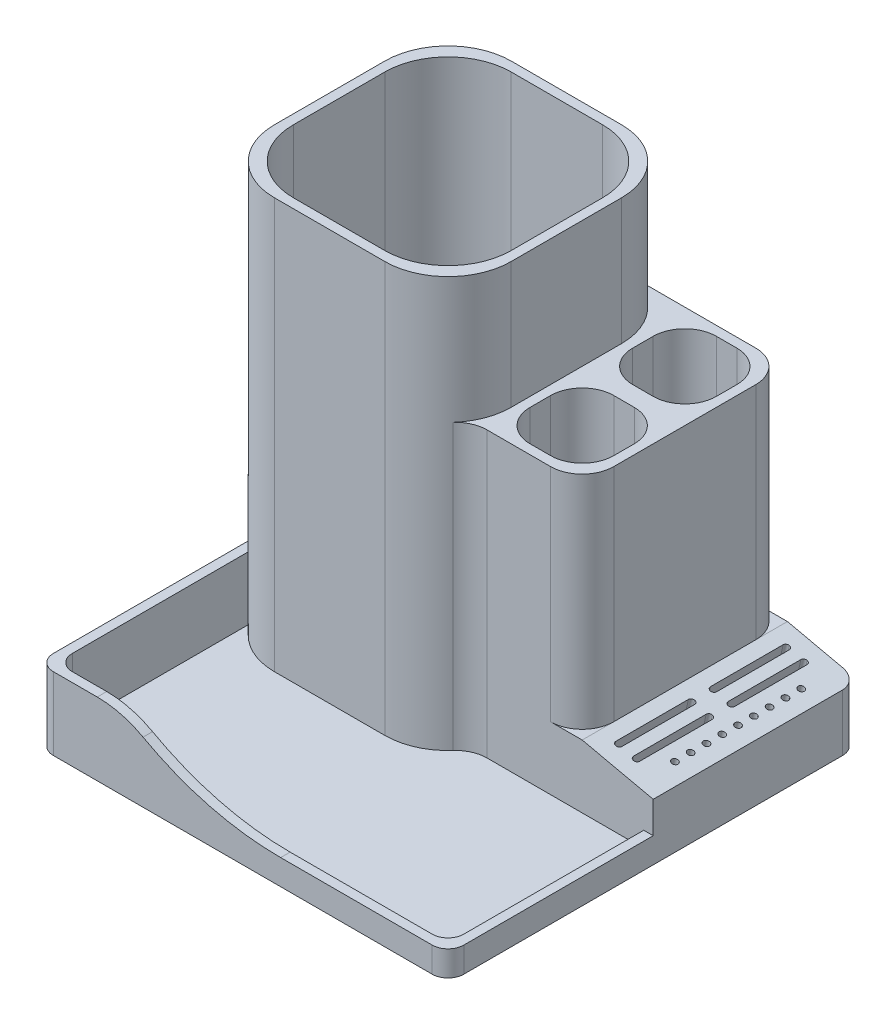
SolidWorks part; units mm, degrees
ref_plane "Спереди" through (0, 0, 0) normal (0, 0, 1) x (1, 0, 0)
ref_plane "Сверху" through (0, 0, 0) normal (0, 1, 0) x (1, 0, 0)
ref_plane "Справа" through (0, 0, 0) normal (1, 0, 0) x (0, 0, -1)
sketch "Эскиз1" plane through (0, 0, 0) normal (0, 1, 0) x (1, 0, 0)
  line L1 (0, 0) -> (-130, 0)
  line L2 (0, 0) -> (0, 130)
  line L3 (0, 130) -> (-130, 130)
  line L4 (-130, 0) -> (-130, 130)
  dimension "D1" = 130
  dimension "D2" = 130
extrude "Бобышка-Вытянуть1" add sketch "Эскиз1" along normal blind 3
sketch "Эскиз2" plane through (0, 3, 0) normal (0, 1, 0) x (1, 0, 0)
  line L0 (-130, 55) -> (-55, 130) construction
  line L1 (-130, 130) -> (-55, 130)
  line L2 (-130, 130) -> (-130, 55)
  line L3 (-130, 55) -> (-55, 55)
  line L4 (-55, 130) -> (-55, 55)
  line L5 (-130, 130) -> (-55, 55) construction
  line L6 (-55, 55) -> (-54.4683, 54.7826) construction
  line L8 (-127, 127) -> (-58, 127)
  line L9 (-127, 127) -> (-127, 58)
  line L10 (-127, 58) -> (-58, 58)
  line L11 (-58, 127) -> (-58, 58)
  line L12 (-127, 127) -> (-58, 58) construction
  line L13 (-127, 58) -> (-58, 127) construction
  point P5 (-92.5, 92.5)
  dimension "D1" = 3
  dimension "D2" = 75
extrude "Бобышка-Вытянуть2" add sketch "Эскиз2" along normal blind 130
sketch "Эскиз3" plane through (0, 3, 0) normal (0, 1, 0) x (1, 0, 0)
  line L0 (-55, 97.5) -> (-22.5, 130) construction
  line L1 (-55, 130) -> (-22.5, 130)
  line L2 (-55, 130) -> (-55, 97.5)
  line L3 (-55, 97.5) -> (-22.5, 97.5)
  line L4 (-22.5, 130) -> (-22.5, 97.5)
  line L5 (-55, 97.5) -> (-22.5, 97.5)
  line L6 (-55, 97.5) -> (-55, 65)
  line L7 (-55, 65) -> (-22.5, 65)
  line L8 (-22.5, 97.5) -> (-22.5, 65)
  line L9 (-22.5, 130) -> (-31.9264, 129.8019) construction
  line L10 (-55, 130) -> (-22.5, 97.5) construction
  line L11 (-55, 65) -> (-22.5, 97.5) construction
  line L12 (-55, 97.5) -> (-22.5, 65) construction
  line L14 (-52, 127) -> (-25.5, 127)
  line L15 (-52, 127) -> (-52, 100.5)
  line L16 (-52, 100.5) -> (-25.5, 100.5)
  line L17 (-25.5, 127) -> (-25.5, 100.5)
  line L18 (-52, 127) -> (-25.5, 100.5) construction
  line L19 (-52, 100.5) -> (-25.5, 127) construction
  line L20 (-52, 94.5) -> (-25.5, 94.5)
  line L21 (-52, 94.5) -> (-52, 68)
  line L22 (-52, 68) -> (-25.5, 68)
  line L23 (-25.5, 94.5) -> (-25.5, 68)
  line L24 (-52, 94.5) -> (-25.5, 68) construction
  line L25 (-52, 68) -> (-25.5, 94.5) construction
  point P7 (-38.75, 113.75)
  point P13 (-38.75, 81.25)
  line M1 (-55, 130) -> (-55, 55)
  line M6 (0, 130) -> (-55, 130)
  dimension "D1" = 32.5
  dimension "D2" = 32.5
  dimension "D3" = 32.5
  dimension "D4" = 3
  dimension "D5" = 3
  dimension "D6" = 3
  dimension "D7" = 3
extrude "Бобышка-Вытянуть3" add sketch "Эскиз3" along normal blind 90 contours L4 L3 L14 L17 L16 L15 M6 M1 | L8 L3 L7 L20 L23 L22 L21 M1 region at (-38.75, 3, -129.5404) region at (-38.75, 3, -97.0404)
fillet "Скругление2" radius 20 2 edges at (-130, 66.5, -130) (-127, 68, -127)
fillet "Скругление3" radius 20 4 edges at (-58, 68, -58) (-55, 68, -55) (-58, 68, -127)
sketch "Эскиз4" plane through (0, 3, 0) normal (0, 1, 0) x (1, 0, 0)
  line L0 (-130, 0) -> (0, 0) construction
  line L1 (-130, 55) -> (-127, 55)
  line L2 (-130, 55) -> (-130, 0)
  line L3 (-130, 0) -> (-127, 0)
  line L4 (-127, 55) -> (-127, 0)
  line L5 (0, 0) -> (0, 130) construction
  line L6 (-127, 0) -> (0, 0)
  line L7 (-127, 0) -> (-127, 3)
  line L8 (-127, 3) -> (0, 3)
  line L9 (0, 0) -> (0, 3)
  line L15 (0, 3) -> (-3, 3)
  line L16 (0, 3) -> (0, 65)
  line L17 (0, 65) -> (-3, 65)
  line L18 (-3, 3) -> (-3, 65)
  line L19 (-22.5, 65) -> (0, 65)
  line M2 (-75, 55) -> (-130, 55)
  line M3 (-130, 55) -> (-130, 0)
  line M4 (-130, 0) -> (0, 0)
  line M5 (0, 0) -> (0, 130)
  dimension "D1" = 3
  dimension "D2" = 3
  dimension "D3" = 3
fillet "Скругление6" radius 10 9 edges at (-57.6795, 48, -65) (-25.5, 48, -100.5) (-25.5, 48, -94.5) (-52, 48, -94.5) (-52, 48, -100.5) (-52, 48, -127) (-52, 48, -68) (-25.5, 48, -68) (-25.5, 48, -127)
extrude "Бобышка-Вытянуть7" add sketch "Эскиз4" along normal blind 20 contours L18 L8 L17 M5 | L8 L4 M4 M5 | L4 M2 M3 M4 region at (-128.5, 3, -27.5) region at (-63.5, 3, -1.5) region at (-1.5, 3, -34)
sketch "Эскиз14" plane through (0, 3, 0) normal (0, 1, 0) x (1, 0, 0)
  line L1 (-22.5, 130) -> (0, 130)
  line L2 (-22.5, 130) -> (-22.5, 65)
  line L3 (-22.5, 65) -> (0, 65)
  line L4 (0, 130) -> (0, 65)
extrude "Бобышка-Вытянуть8" add sketch "Эскиз14" along normal blind 20
sketch "Эскиз15" plane through (0, 0, 0) normal (0, 0, 1) x (1, 0, 0)
  line L0 (-130, 23) -> (0, 23) construction
  line L1 (-102.7518, 23) -> (0, 23)
  line L2 (-102.7518, 23) -> (-102.7518, 8)
  line L3 (-102.7518, 8) -> (0, 8)
  line L4 (0, 23) -> (0, 8)
  line L5 (0, 23) -> (0, 0) construction
  point P9 (0, 0)
  line M2 (0, 0) -> (0, 23)
  line M3 (0, 23) -> (-130, 23)
  dimension "D1" = 8
extrude "Вырез-Вытянуть6" cut sketch "Эскиз15" against normal blind 3 contours L3 M3 M2 region at (-51.3759, 15.5, 0)
fillet "Скругление7" radius 90 1 edges at (-102.7518, 8, -1.5)
fillet "Скругление8" radius 30 1 edges at (-102.7518, 23, -1.5)
sketch "Эскиз17" plane through (0, 0, 0) normal (1, 0, 0) x (0, 0, -1)
  line L1 (3, 8) -> (65, 8)
  line L2 (3, 8) -> (3, 23)
  line L3 (3, 23) -> (65, 23)
  line L4 (65, 8) -> (65, 23)
  point P6 (0, 0)
  point P7 (0, 0)
extrude "Вырез-Вытянуть8" cut sketch "Эскиз17" against normal blind 3
fillet "Скругление9" radius 5 5 edges at (0, 11.5, -130) (-3, 5.5, -3) (0, 4, 0) (-127, 13, -3) (-130, 11.5, 0)
fillet "Скругление11" radius 20 1 edges at (-127, 68, -58)
fillet "Скругление12" radius 20 1 edges
fillet "Скругление13" radius 10 2 edges at (-22.5, 58, -65) (-22.5, 58, -130)
sketch "Эскиз18" plane through (0, 0, -65) normal (0, 0, 1) x (1, 0, 0)
  line L0 (-22.5, 23) -> (0, 18)
  line L1 (0, 23) -> (-32.5, 23) construction
  line L2 (-22.5, 93) -> (-22.5, 23) construction
  line L3 (0, 8) -> (0, 23) construction
  line L4 (0, 18) -> (0, 23)
  line L5 (0, 23) -> (-22.5, 23)
  dimension "D1" = 5
extrude "Вырез-Вытянуть9" cut sketch "Эскиз18" against normal blind 300
sketch "Эскиз19" plane through (3.8118, 17.1529, 0) normal (0.2169, 0.9762, 0) x (0.9762, -0.2169, 0)
  line L0 (-15.4292, 130) -> (-15.4292, 65) construction
  line L1 (-26.9536, 130) -> (-3.9047, 130)
  line L2 (-26.9536, 130) -> (-26.9536, 65)
  line L3 (-26.9536, 65) -> (-3.9047, 65)
  line L4 (-3.9047, 130) -> (-3.9047, 65)
  line L5 (-16.4292, 100) -> (-16.4292, 125)
  line L6 (-16.4292, 70) -> (-14.4292, 70)
  line L7 (-16.4292, 70) -> (-16.4292, 95)
  line L8 (-16.4292, 95) -> (-14.4292, 95)
  line L9 (-14.4292, 70) -> (-14.4292, 95)
  line L10 (-16.4292, 70) -> (-14.4292, 95) construction
  line L11 (-16.4292, 95) -> (-14.4292, 70) construction
  line L12 (-16.4292, 100) -> (-14.4292, 100)
  line L13 (-14.4292, 100) -> (-14.4292, 125)
  line L14 (-16.4292, 125) -> (-14.4292, 125)
  line L15 (-15.4292, 130) -> (-3.9047, 130) construction
  line L16 (-9.667, 130) -> (-9.667, 65) construction
  line L17 (-26.9536, 97.5) -> (-3.9047, 97.5) construction
  line L18 (-26.9536, 130) -> (-15.4292, 130) construction
  line L19 (-15.4292, 130) -> (-21.1914, 130) construction
  line L20 (-21.1914, 130) -> (-21.1914, 65) construction
  line L21 (-16.4292, 70) -> (-16.1759, 70) construction
  line L22 (-16.4292, 70) -> (-26.9536, 70) construction
  line L23 (-22.1914, 125) -> (-22.1914, 100)
  line L24 (-22.1914, 95) -> (-20.1914, 95)
  line L25 (-22.1914, 95) -> (-22.1914, 70)
  line L26 (-22.1914, 70) -> (-20.1914, 70)
  line L27 (-20.1914, 95) -> (-20.1914, 70)
  line L28 (-22.1914, 95) -> (-20.1914, 70) construction
  line L29 (-22.1914, 70) -> (-20.1914, 95) construction
  line L30 (-22.1914, 125) -> (-20.1914, 125)
  line L31 (-20.1914, 125) -> (-20.1914, 100)
  line L32 (-22.1914, 100) -> (-20.1914, 100)
  circle A0 centre (-9.667, 97.5) radius 1
  circle A1 centre (-9.667, 102.5) radius 1
  circle A2 centre (-9.667, 107.5) radius 1
  circle A3 centre (-9.667, 112.5) radius 1
  circle A4 centre (-9.667, 117.5) radius 1
  circle A5 centre (-9.667, 92.5) radius 1
  circle A6 centre (-9.667, 87.5) radius 1
  circle A7 centre (-9.667, 82.5) radius 1
  circle A8 centre (-9.667, 77.5) radius 1
  point P8 (-15.4292, 82.5)
  point P23 (-21.1914, 82.5)
  dimension "D5" = 5
  dimension "D1" = 25
  dimension "D2" = 2
  dimension "D3" = 5
  dimension "D6" = 2
  dimension "D4" = 2
  dimension "D7" = 2
  dimension "D8" = 5
extrude "Вырез-Вытянуть12" cut sketch "Эскиз19" against normal blind 18 contours A1 | A2 | A3 | A4 | A0 | A5 | A6 | A7 | A8 region at (-5.625, 19.25, -97.5) region at (-5.625, 19.25, -102.5) region at (-5.625, 19.25, -107.5) region at (-5.625, 19.25, -112.5) region at (-5.625, 19.25, -117.5) region at (-5.625, 19.25, -92.5) region at (-5.625, 19.25, -87.5) region at (-5.625, 19.25, -82.5) region at (-5.625, 19.25, -77.5)
extrude "Вырез-Вытянуть13" cut sketch "Эскиз19<4>" against normal blind 20 contours L23 L32 L31 L30 | L27 L24 L25 L26 | L14 L5 L12 L13 | L6 L9 L8 L7 region at (-11.25, 20.5, -112.5) region at (-11.25, 20.5, -82.5) region at (-16.875, 21.75, -112.5) region at (-16.875, 21.75, -82.5)
sketch "Эскиз19<4>" plane through (3.8118, 17.1529, 0) normal (0.2169, 0.9762, 0) x (0.9762, -0.2169, 0) same geometry as "Эскиз19"
fillet "Скругление15" radius 1 16 edges at (-14.3955, 10.9551, -100) (-20.0205, 12.2051, -100) (-14.3955, 10.9551, -125) (-20.0205, 12.2051, -125) (-18.0681, 11.7712, -100) (-12.4431, 10.5212, -100) (-12.4431, 10.5212, -125) (-18.0681, 11.7712, -125) (-12.4431, 10.5212, -95) (-18.0681, 11.7712, -95) (-14.3955, 10.9551, -95) (-20.0205, 12.2051, -95) (-12.4431, 10.5212, -70) (-18.0681, 11.7712, -70) (-14.3955, 10.9551, -70) (-20.0205, 12.2051, -70)
